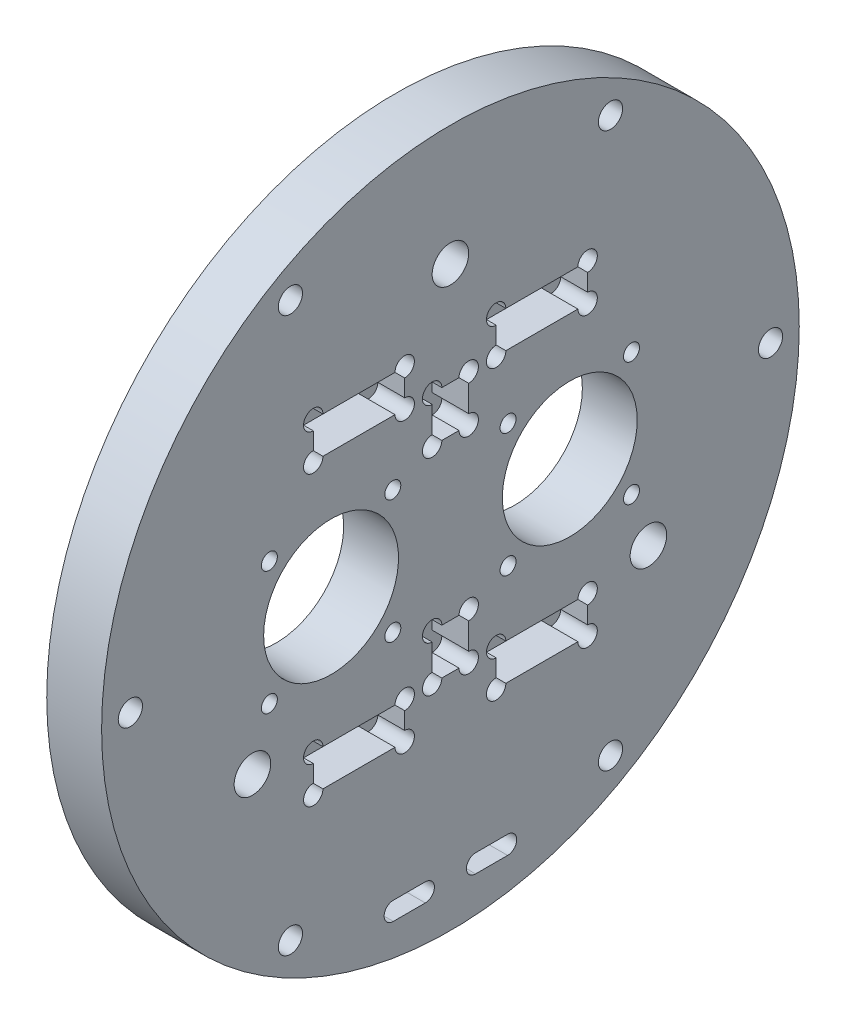
SolidWorks part; units mm, degrees
ref_plane "Front Plane" through (0, 0, 0) normal (0, 0, 1) x (1, 0, 0)
ref_plane "Top Plane" through (0, 0, 0) normal (0, 1, 0) x (1, 0, 0)
ref_plane "Right Plane" through (0, 0, 0) normal (1, 0, 0) x (0, 0, -1)
sketch "Sketch1" plane through (0, 0, 0) normal (1, 0, 0) x (0, 0, -1)
  line L0 (0, -76.29) -> (0, 76.29) construction
  line L1 (-76.29, 0) -> (76.29, 0) construction
  line L2 (26.1, 0) -> (39.5969, 13.4969) construction
  circle A0 centre (0, 0) radius 76.29
  circle A1 centre (0, 50) radius 4
  circle A2 centre (43.3013, -25) radius 4
  circle A3 centre (-43.3013, -25) radius 4
  circle A4 centre (26.1, 0) radius 14.75
  circle A5 centre (-26.1, 0) radius 14.75
  circle A6 centre (39.5969, 13.4969) radius 1.75
  circle A7 centre (39.5969, -13.4969) radius 1.75
  circle A8 centre (12.6031, -13.4969) radius 1.75
  circle A9 centre (12.6031, 13.4969) radius 1.75
  circle A10 centre (-39.5969, -13.4969) radius 1.75
  circle A11 centre (-12.6031, -13.4969) radius 1.75
  circle A12 centre (-12.6031, 13.4969) radius 1.75
  circle A13 centre (-39.5969, 13.4969) radius 1.75
  circle A14 centre (26.1, 0) radius 22.1 construction
  circle A15 centre (-26.1, 0) radius 22.1 construction
  point P12 (0, 0)
  point P29 (26.1, 0)
  point P37 (-4, 0)
  point P40 (4, 0)
  dimension "D1" = 152.58
  dimension "D2" = 8
  dimension "D5" = 29.5
  dimension "D7" = 3.5
  dimension "D11" = 44.2
  dimension "D3" = 50
  dimension "D4" = 3
  dimension "D6" = 8
  dimension "D8" = 19.0875
  dimension "D10" = 45
  dimension "D9" = 4
extrude "Boss-Extrude1" add sketch "Sketch1" along normal blind 12
sketch "Sketch2" plane through (12, 0, 0) normal (1, 0, 0) x (0, 0, -1)
  line L0 (-97.5918, 0) -> (102.3086, 0) construction
  line L1 (0, 96.3466) -> (0, -103.9448) construction
  line L2 (10, -27.5) -> (10, -35.5)
  line L3 (-30, -27.5) -> (-10, -27.5)
  line L4 (-30, -27.5) -> (-30, -35.5)
  line L5 (-30, -35.5) -> (-10, -35.5)
  line L6 (-10, -27.5) -> (-10, -35.5)
  line L7 (30, -27.5) -> (10, -27.5)
  line L8 (30, -27.5) -> (30, -35.5)
  line L9 (30, -35.5) -> (10, -35.5)
  line L10 (-30, 27.5) -> (-30, 35.5)
  line L11 (-30, 35.5) -> (-10, 35.5)
  line L12 (-10, 27.5) -> (-10, 35.5)
  line L13 (-30, 27.5) -> (-10, 27.5)
  line L14 (10, 27.5) -> (10, 35.5)
  line L15 (30, 35.5) -> (10, 35.5)
  line L16 (30, 27.5) -> (10, 27.5)
  line L17 (30, 27.5) -> (30, 35.5)
  line L18 (-4, -17.5) -> (4, -17.5)
  line L19 (-4, 27.5) -> (4, 27.5)
  line L20 (-4, 27.5) -> (-4, 17.5)
  line L21 (-4, 17.5) -> (4, 17.5)
  line L22 (4, 27.5) -> (4, 17.5)
  line L23 (-4, -27.5) -> (-4, -17.5)
  line L24 (-4, -27.5) -> (4, -27.5)
  line L25 (4, -27.5) -> (4, -17.5)
  line L26 (27.8787, -35.5) -> (30, -33.3787) construction
  line L27 (-42.3534, -68.29) -> (39.6493, -68.29) construction
  line L28 (-5.5, -68.29) -> (-5.5, -64.29)
  line L29 (12.5, -68.29) -> (5.5, -68.29)
  line L30 (12.5, -68.29) -> (12.5, -64.29)
  line L31 (12.5, -64.29) -> (5.5, -64.29)
  line L32 (5.5, -68.29) -> (5.5, -64.29)
  line L33 (-12.5, -64.29) -> (-5.5, -64.29)
  line L34 (-12.5, -68.29) -> (-12.5, -64.29)
  line L35 (-12.5, -68.29) -> (-5.5, -68.29)
  circle A0 centre (30, -35.5) radius 2.1213 construction
  circle A1 centre (0, 0) radius 76.29 construction
  point P23 (0, 27.5)
  point P31 (30, -33.3787)
  point P32 (0, -76.29)
  point P33 (27.8787, -35.5)
  dimension "D1" = 27.5
  dimension "D2" = 8
  dimension "D3" = 20
  dimension "D4" = 20
  dimension "D5" = 8
  dimension "D6" = 10
  dimension "D7" = 8
  dimension "D8" = 4
  dimension "D9" = 7
  dimension "D10" = 25
extrude "Cut-Extrude1" cut sketch "Sketch2" against normal blind 8
sketch "Sketch3" plane through (0, 0, 0) normal (-1, 0, 0) x (0, 0, 1)
  circle A0 centre (-70, 0) radius 2.65
  circle A1 centre (-35, 60.6218) radius 2.65
  circle A2 centre (35, 60.6218) radius 2.65
  circle A3 centre (70, 0) radius 2.65
  circle A4 centre (35, -60.6218) radius 2.65
  circle A5 centre (-35, -60.6218) radius 2.65
  point P16 (0, 0)
  dimension "D2" = 5.3
  dimension "D1" = 70
  dimension "D3" = 6
extrude "Cut-Extrude2" cut sketch "Sketch3" against normal up to next
sketch "Sketch4" plane through (12, 0, 0) normal (1, 0, 0) x (0, 0, -1)
  line L0 (12.5, -68.29) -> (12.5, -64.29) construction
  line L2 (5.5, -64.29) -> (5.5, -68.29) construction
  line L3 (-5.5, -68.29) -> (-5.5, -64.29) construction
  line L4 (-12.5, -64.29) -> (-12.5, -68.29) construction
  circle A0 centre (-10, -35.5) radius 2.1213
  circle A1 centre (-10, -27.5) radius 2.1213
  circle A2 centre (-30, -27.5) radius 2.1213
  circle A3 centre (-30, -35.5) radius 2.1213
  circle A4 centre (12.5, -66.29) radius 2
  circle A5 centre (5.5, -66.29) radius 2
  circle A6 centre (-5.5, -66.29) radius 2
  circle A7 centre (-12.5, -66.29) radius 2
  circle A12 centre (10, -35.5) radius 2.1213
  circle A13 centre (10, -27.5) radius 2.1213
  circle A14 centre (30, -27.5) radius 2.1213
  circle A15 centre (30, -35.5) radius 2.1213
  circle A16 centre (4, -27.5) radius 2.1213
  circle A17 centre (-4, -27.5) radius 2.1213
  circle A18 centre (-4, -17.5) radius 2.1213
  circle A19 centre (4, -17.5) radius 2.1213
  circle A20 centre (4, 27.5) radius 2.1213
  circle A21 centre (-4, 27.5) radius 2.1213
  circle A22 centre (-4, 17.5) radius 2.1213
  circle A23 centre (4, 17.5) radius 2.1213
  circle A24 centre (10, 27.5) radius 2.1213
  circle A25 centre (10, 35.5) radius 2.1213
  circle A26 centre (30, 35.5) radius 2.1213
  circle A27 centre (30, 27.5) radius 2.1213
  circle A28 centre (-10, 35.5) radius 2.1213
  circle A29 centre (-10, 27.5) radius 2.1213
  circle A30 centre (-30, 27.5) radius 2.1213
  circle A31 centre (-30, 35.5) radius 2.1213
  point P2 (-12.1213, -35.5)
  point P5 (-10, -33.3787)
  dimension "D1" = 3
extrude "Cut-Extrude3" cut sketch "Sketch4" against normal up to surface (8 mm away) up to face at (4, -31.5, 20)
